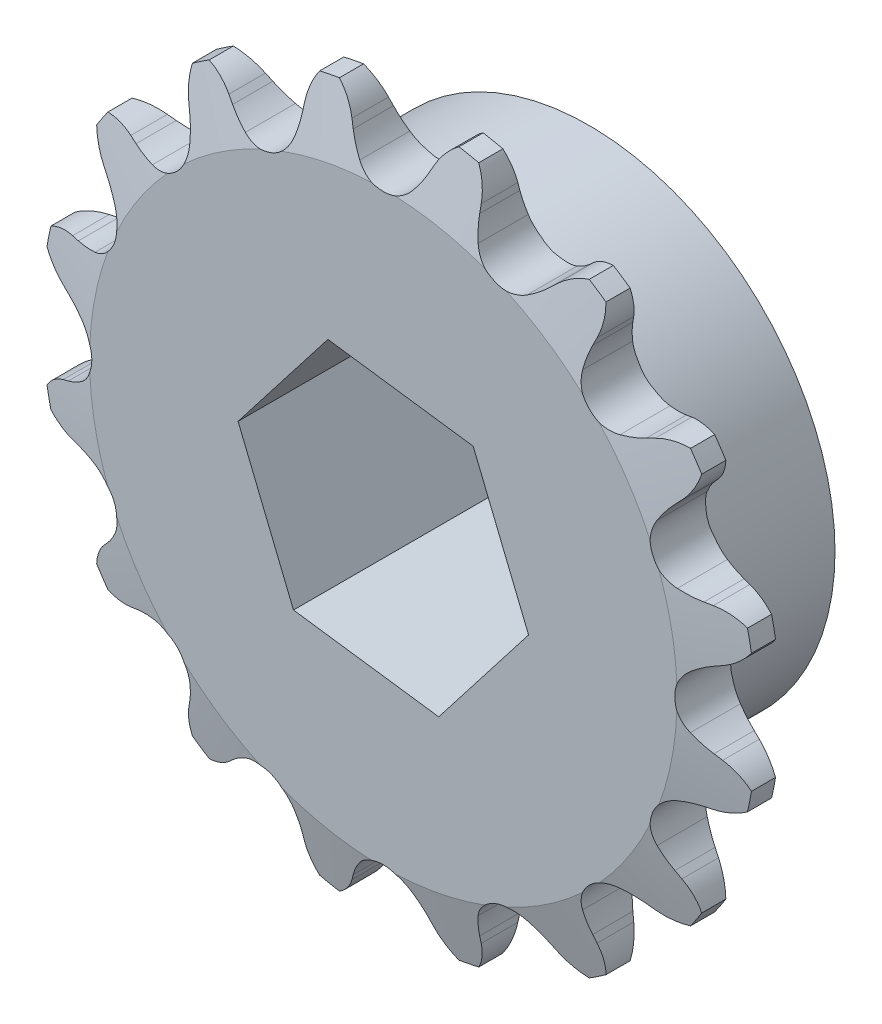
SolidWorks part; units mm, degrees
ref_plane "Front Plane" through (0, 0, 0) normal (0, 0, 1) x (1, 0, 0)
ref_plane "Top Plane" through (0, 0, 0) normal (0, 1, 0) x (1, 0, 0)
ref_plane "Right Plane" through (0, 0, 0) normal (1, 0, 0) x (0, 0, -1)
ref_axis "Axis1" through (0, 0, -88.99) along (0, 0, 1)
sketch "Sprocket-BaseSketch" plane through (0, 0, 0) normal (1, 0, 0) x (0, 0, -1)
  line L0 (1.397, 0) -> (1.397, 14.6918)
  line L1 (1.397, 14.6918) -> (0.6032, 17.8668)
  line L2 (0.6032, 17.8668) -> (-0.6032, 17.8668)
  line L3 (-0.6032, 17.8668) -> (-1.397, 14.6918)
  line L4 (-1.397, 14.6918) -> (-1.397, 0)
  line L5 (-1.397, 0) -> (1.397, 0)
  line L6 (5.588, 0) -> (-1.7463, 0) construction
  dimension "Hub Surface" = 1.397
  dimension "RightSide (1)" = 0.7938
  dimension "RightSide (2)" = 3.175
  dimension "OD" = 17.8668
  dimension "LeftSide (1)" = 0.7938
  dimension "LeftSide (2)" = 3.175
  dimension "Tooth Width" = 2.794
revolve "25 (04C) ANSI (ISO) Chain Number, 1.281in P.D." add sketch "Sprocket-BaseSketch" angle 360 about L6
sketch "Tooth-Sketch" plane through (0, 0, 0) normal (0, 0, 1) x (1, 0, 0)
  line L0 (0, 0) -> (0, 21.6994) construction
  line L1 (1.896, 16.1459) -> (2.0514, 16.491)
  line L2 (-1.896, 16.1459) -> (-2.0514, 16.491)
  line L3 (0, 16.2745) -> (6.228, 15.0357) construction
  line L4 (0, 16.2745) -> (-6.228, 15.0357) construction
  arc A0 (-1.3237, 15.2121) -> (1.3237, 15.2121) centre (0, 16.2745) ccw
  arc A1 (1.3237, 15.2121) -> (1.896, 16.1459) centre (-2.0601, 17.928) ccw
  arc A2 (-1.3237, 15.2121) -> (-1.896, 16.1459) centre (2.0601, 17.928) cw
  arc A3 (2.0514, 16.491) -> (4.534, 18.0955) centre (4.534, 15.3726) cw
  arc A4 (-2.0514, 16.491) -> (-4.534, 18.0955) centre (-4.534, 15.3726) ccw
  arc A5 (4.534, 18.0955) -> (-4.534, 18.0955) centre (0, 0) ccw
extrude "Tooth-Cut, Number of teeth: 16" cut sketch "Tooth-Sketch" against normal through all and the other way through all
pattern_circular "Tooth Pattern, 16 / 16" count 16 every 22.5 about axis through (0, 0, -88.99) along (0, 0, 1) of "Tooth-Cut, Number of teeth: 16"
sketch "Sketch3" plane through (0, 0, 0) normal (1, 0, 0) x (0, 0, -1)
  line L0 (-9.906, 0) -> (9.906, 0) construction
  line L1 (1.397, 0) -> (1.397, 12.3031)
  line L2 (1.397, 12.3031) -> (8.89, 12.3031)
  line L3 (8.89, 12.3031) -> (8.89, 0)
  line L4 (8.89, 0) -> (1.397, 0)
  dimension "Hub Mounting" = 1.397
  dimension "Hub OD" = 12.3031
  dimension "Hub Width" = 7.493
revolve "Hub-Revolve1" add sketch "Sketch3" angle 360 about L0
sketch "Sketch4" plane through (0, 0, -8.89) normal (0, 0, -1) x (-1, 0, 0)
  circle A0 centre (0, 0) radius 6.35
  dimension "Bore Diameter " = 12.7
extrude "Cut-Extrude1" cut sketch "Sketch4" against normal through all
sketch "Sketch5" [suppressed] plane through (0, 0, 0) normal (1, 0, 0) x (0, 0, -1)
  line L0 (8.89, 0) -> (-1.397, 0) construction
  line L1 (8.89, -12.3031) -> (8.89, 12.3031) construction
  line L2 (-1.397, 0.5825) -> (-1.397, -0.5825) construction
ref_plane "Plane1" [suppressed] through (0, 0, 0) normal (-0.1951, 0.9808, 0) x (-0.9808, -0.1951, 0)
sketch "Sketch7" [suppressed] plane through (0, 0, 0) normal (1, 0, 0) x (0, 0, -1)
  line L0 (8.89, 0) -> (8.89, 6.35) construction
ref_plane "Plane2" [suppressed] through (-1.215, 6.1083, 0) normal (-0.1951, 0.9808, 0) x (-0.9808, -0.1951, 0)
sketch "Sketch8" [suppressed] plane through (-1.215, 6.1083, 0) normal (-0.1951, 0.9808, 0) x (-0.9808, -0.1951, 0)
  line L0 (-12.3031, -5.1435) -> (12.3031, -5.1435) construction
  line L1 (-12.3031, -1.397) -> (-12.3031, -8.89) construction
  line L2 (12.3031, -8.89) -> (12.3031, -1.397) construction
  line L3 (0, -5.1435) -> (0, -1.397) construction
  line L4 (-12.3031, -1.397) -> (12.3031, -1.397) construction
  line L5 (0, -3.2703) -> (0, -5.1435) construction
  circle A0 centre (0, -5.1435) radius 1.8732
extrude "Cut-Extrude2" [suppressed] cut sketch "Sketch8" along normal through all draft 1 and the other way blind 2.54 draft 1 draft outward yes
sketch "Sketch9" [suppressed] plane through (-1.215, 6.1083, 0) normal (-0.1951, 0.9808, 0) x (-0.9808, -0.1951, 0)
  line L0 (0, -5.1435) -> (1.8705, -5.1435) construction
  line L1 (1.8705, -5.1435) -> (1.9763, -5.1435) construction
  line L2 (1.9234, -5.1435) -> (1.9234, -8.89) construction
  line L3 (-12.3031, -8.89) -> (12.3031, -8.89) construction
  circle A0 centre (0, -5.1435) radius 1.9234
  circle A1 centre (0, -5.1435) radius 1.8732 construction
  spline S0 degree 3 poles (1.4639, -6.3175) (1.6045, -6.1152) (1.664, -6.0088) (1.7618, -5.7853) (1.8004, -5.6668) (1.8531, -5.4263) (1.8676, -5.3047) (1.8726, -5.0584) (1.8627, -4.9334) (1.798, -4.5712) (1.7062, -4.3373) (1.5097, -4.0296) (1.4333, -3.9323) (1.2645, -3.7562) (1.1724, -3.6771) (0.9728, -3.537) (0.8645, -3.4759) (0.6412, -3.3775) (0.5252, -3.3393) (0.1632, -3.2589) (-0.0869, -3.2538) (-0.4521, -3.3195) (-0.5699, -3.3531) (-0.7977, -3.4428) (-0.9085, -3.4996) (-1.2159, -3.6976) (-1.3953, -3.871) (-1.6727, -4.2697) (-1.7737, -4.4996) (-1.8528, -4.8584) (-1.8676, -4.9829) (-1.8725, -5.2291) (-1.863, -5.3514) (-1.8198, -5.5941) (-1.786, -5.7141) (-1.697, -5.9416) (-1.6414, -6.0511) (-1.5091, -6.2584) (-1.4339, -6.3539) (-1.2659, -6.5295) (-1.1719, -6.6103) (-0.9722, -6.7503) (-0.8663, -6.8102) (-0.6422, -6.9092) (-0.5236, -6.9481) (-0.1649, -7.0276) (0.0882, -7.0328) (0.4502, -6.9679) (0.5701, -6.9339) (0.7988, -6.8438) (0.9072, -6.7881) (1.1128, -6.6559) (1.2099, -6.5789) (1.3848, -6.41) (1.4639, -6.3175) (1.6045, -6.1152) (1.664, -6.0088) knots -0.03125 -0.03125 0 0 0.03125 0.03125 0.0625 0.0625 0.09375 0.09375 0.125 0.125 0.1875 0.1875 0.21875 0.21875 0.25 0.25 0.28125 0.28125 0.3125 0.3125 0.375 0.375 0.40625 0.40625 0.4375 0.4375 0.5 0.5 0.5625 0.5625 0.59375 0.59375 0.625 0.625 0.65625 0.65625 0.6875 0.6875 0.71875 0.71875 0.75 0.75 0.78125 0.78125 0.8125 0.8125 0.875 0.875 0.90625 0.90625 0.9375 0.9375 0.96875 0.96875 1 1 1.03125 1.03125 1.0625 only from (1.5342, -6.2163) to (1.5342, -6.2163) construction
  spline S1 degree 3 poles (1.9146, -5.6519) (1.9899, -5.2667) (1.9881, -5.0012) (1.8854, -4.4958) (1.7828, -4.251) (1.5671, -3.9304) (1.4835, -3.8292) (1.3001, -3.6471) (1.2004, -3.5657) (0.9849, -3.4226) (0.8689, -3.361) (0.6303, -3.2631) (0.5066, -3.2259) (0.25, -3.1757) (0.121, -3.1637) (-0.1371, -3.1648) (-0.2678, -3.1782) (-0.5222, -3.2301) (-0.6453, -3.2682) (-0.8836, -3.3683) (-0.9993, -3.4309) (-1.3197, -3.6476) (-1.5058, -3.8358) (-1.7898, -4.2652) (-1.8905, -4.5107) (-1.9646, -4.891) (-1.977, -5.0223) (-1.9759, -5.2813) (-1.9628, -5.4096) (-1.9113, -5.664) (-1.8727, -5.7895) (-1.7732, -6.0272) (-1.7122, -6.1409) (-1.5666, -6.3573) (-1.4843, -6.4568) (-1.3019, -6.6383) (-1.2005, -6.7212) (-0.9847, -6.8646) (-0.8709, -6.925) (-0.6318, -7.0234) (-0.5056, -7.0613) (-0.1253, -7.1357) (0.1407, -7.1346) (0.646, -7.0318) (0.8907, -6.9291) (1.2112, -6.7129) (1.3124, -6.6291) (1.4941, -6.4457) (1.5753, -6.3459) (1.7184, -6.13) (1.7797, -6.0141) (1.8774, -5.7756) (1.9146, -5.6519) (1.9899, -5.2667) (1.9881, -5.0012) knots -0.03125 -0.03125 0 0 0.0625 0.0625 0.125 0.125 0.15625 0.15625 0.1875 0.1875 0.21875 0.21875 0.25 0.25 0.28125 0.28125 0.3125 0.3125 0.34375 0.34375 0.375 0.375 0.4375 0.4375 0.5 0.5 0.53125 0.53125 0.5625 0.5625 0.59375 0.59375 0.625 0.625 0.65625 0.65625 0.6875 0.6875 0.71875 0.71875 0.75 0.75 0.8125 0.8125 0.875 0.875 0.90625 0.90625 0.9375 0.9375 0.96875 0.96875 1 1 1.0625 1.0625 1.125 only from (1.9397, -5.5235) to (1.9397, -5.5235) construction
extrude "Extrude1" [suppressed] add sketch "Sketch9" along normal up to surface and the other way blind 2.54 up to face at (12.3031, 0, -1.397)
sketch "Sketch10" [suppressed] plane through (-1.215, 6.1083, 0) normal (-0.1951, 0.9808, 0) x (-0.9808, -0.1951, 0)
  line L0 (0, -5.1435) -> (1.9234, -5.1435) construction
  line L1 (0.9617, -5.1435) -> (0.9617, -3.4778) construction
  line L3 (0, -4.033) -> (-0.9617, -4.5883)
  line L4 (-0.9617, -4.5883) -> (-0.9617, -5.6987)
  line L5 (-0.9617, -5.6987) -> (0, -6.254)
  line L6 (0, -6.254) -> (0.9617, -5.6987)
  line L7 (0.9617, -5.6987) -> (0.9617, -4.5883)
  line L8 (0.9617, -4.5883) -> (0, -4.033)
  circle A0 centre (0, -5.1435) radius 1.9234 construction
  circle A1 centre (0, -5.1435) radius 0.9617 construction
extrude "Cut-Extrude3" [suppressed] cut sketch "Sketch10" along normal through all from offset 2.54
pattern_circular "CirPattern1" [suppressed] count 2 over 90 about axis through (0, 0, 9.906) along (0, 0, -1) of bodies 108
sketch "Sketch11" plane through (0, 0, -8.89) normal (0, 0, -1) x (-1, 0, 0)
  line L1 (-2.7711, -6.7885) -> (4.4935, -5.7941)
  line L2 (4.4935, -5.7941) -> (7.2646, 0.9944)
  line L3 (7.2646, 0.9944) -> (2.7711, 6.7885)
  line L4 (2.7711, 6.7885) -> (-4.4935, 5.7941)
  line L5 (-4.4935, 5.7941) -> (-7.2646, -0.9944)
  line L6 (-7.2646, -0.9944) -> (-2.7711, -6.7885)
  circle A0 centre (0, 0) radius 6.35 construction
  circle A1 centre (0, 0) radius 6.35 construction
  circle A2 centre (0, 0) radius 6.35 construction
extrude "Cut-Extrude4" cut sketch "Sketch11" against normal through all
sketch "Sketch12" [suppressed] plane through (0, 0, -11.303) normal (0, 0, -1) x (-1, 0, 0)
  line L0 (-17.5235, 3.4856) -> (17.5235, -3.4856)
  line L1 (-6.228, -15.0357) -> (0, -16.2745)
  line L2 (6.8508, -1.3627) -> (-6.8508, 1.3627) construction
  line L3 (-17.7837, 2.1778) -> (17.2633, -4.7935)
  line L4 (-5.9678, -13.7278) -> (0.2602, -14.9666)
  circle A0 centre (0, 0) radius 17.8668
  arc A1 (15.1301, 9.5028) -> (14.5694, 10.3419) centre (0, 0) ccw construction
  dimension "D1" = 1.3335
  dimension "D2" = 1.3335
sketch "Sketch13" [suppressed] plane through (0, 0, -11.303) normal (0, 0, -1) x (-1, 0, 0)
  circle A0 centre (0, 0) radius 6.35
  circle A1 centre (0, 0) radius 12.3031
equation "\"D1@Sketch12\" = \"D2@Sketch12\""
